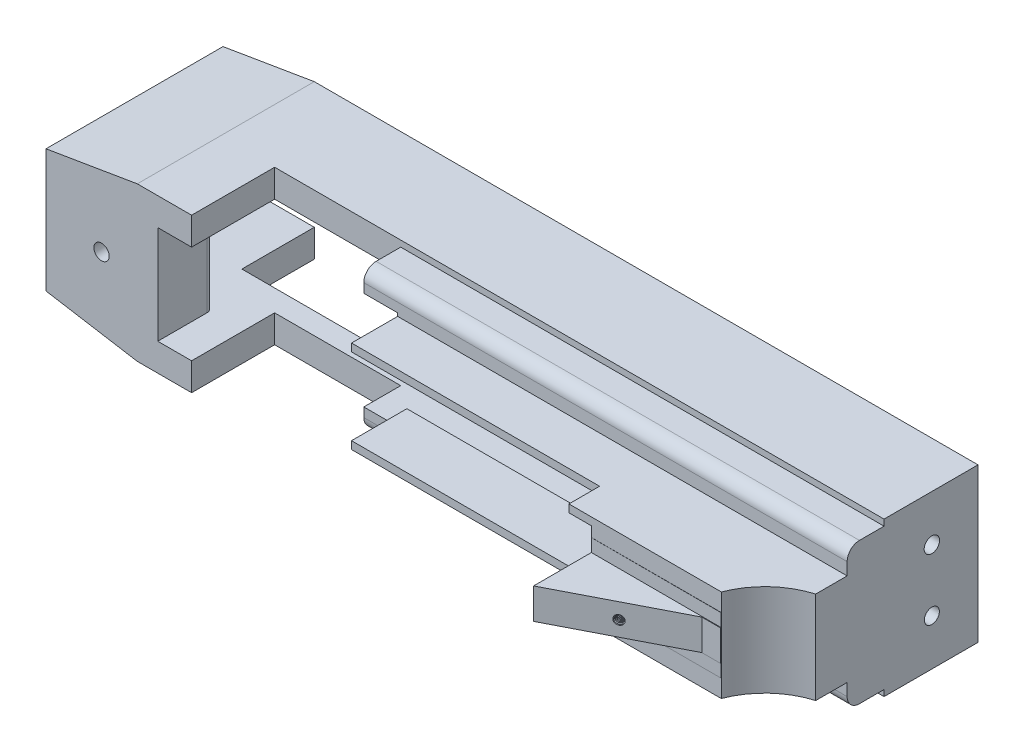
SolidWorks part; units mm, degrees
ref_plane "Front Plane" through (0, 0, 0) normal (0, 0, 1) x (1, 0, 0)
ref_plane "Top Plane" through (0, 0, 0) normal (0, 1, 0) x (1, 0, 0)
ref_plane "Right Plane" through (0, 0, 0) normal (1, 0, 0) x (0, 0, -1)
sketch "Sketch1" plane through (0, 0, 0) normal (0, 0, 1) x (1, 0, 0)
  line L0 (0, 0) -> (245.5, 0)
  line L1 (245.5, 0) -> (245.5, 50)
  line L2 (245.5, 50) -> (0, 50)
  line L3 (0, 50) -> (0, 0)
  dimension "D1" = 245.5
  dimension "D2" = 50
extrude "Boss-Extrude1" add sketch "Sketch1" along normal blind 57.55
sketch "Sketch2" plane through (0, 0, 0) normal (0, 0, -1) x (-1, 0, 0)
  line L0 (0, 9) -> (-205, 9)
  line L1 (0, 50) -> (0, 0) construction
  line L2 (-205, 9) -> (-205, 41)
  line L3 (-205, 41) -> (0, 41)
  line L4 (0, 41) -> (0, 9)
  line L5 (0, 0) -> (-245.5, 0) construction
  line L6 (-245.5, 50) -> (0, 50) construction
  dimension "D1" = 9
  dimension "D2" = 9
  dimension "D3" = 205
extrude "Cut-Extrude1" cut sketch "Sketch2" against normal blind 39.55
sketch "Sketch3" plane through (0, 0, 39.55) normal (0, 0, -1) x (-1, 0, 0)
  line L0 (-10, 9) -> (0, 9)
  line L1 (-205, 9) -> (0, 9) construction
  line L2 (0, 9) -> (0, 41)
  line L3 (0, 41) -> (-10, 41)
  line L4 (0, 41) -> (-205, 41) construction
  line L5 (-10, 41) -> (-10, 9)
  dimension "D1" = 10
extrude "Cut-Extrude2" cut sketch "Sketch3" against normal blind 5
sketch "Sketch4" plane through (0, 0, 39.55) normal (0, 0, -1) x (-1, 0, 0)
  line L0 (0, 9) -> (0, 41) construction
  line L1 (-205, 9) -> (-10, 9) construction
  circle A0 centre (-18.055, 25) radius 2.4875
  dimension "D1" = 4.975
  dimension "D2" = 18.055
  dimension "D3" = 16
extrude "Cut-Extrude3" cut sketch "Sketch4" against normal through all
sketch "Sketch5" plane through (0, 0, 0) normal (0, 0, -1) x (-1, 0, 0)
  line L1 (0, 50) -> (0, 41) construction
  line L4 (0, 45.028) -> (-29.689, 50)
  line L5 (-245.5, 50) -> (0, 50) construction
  line L7 (0, 45.028) -> (0, 51.6223)
  line L8 (0, 51.6223) -> (-29.689, 51.6223)
  line L9 (-29.689, 51.6223) -> (-29.689, 50)
extrude "Cut-Extrude4" cut sketch "Sketch5" against normal through all
sketch "Sketch6" plane through (0, 0, 0) normal (0, 0, -1) x (-1, 0, 0)
  line L1 (0, 9) -> (0, 0) construction
  line L4 (0, 4.972) -> (-29.689, 0)
  line L5 (0, 0) -> (-245.5, 0) construction
  line L7 (-29.689, 0) -> (0.6137, 0)
  line L8 (0.6137, 0) -> (0.6137, 4.972)
  line L9 (0.6137, 4.972) -> (0, 4.972)
extrude "Cut-Extrude5" cut sketch "Sketch6" against normal through all
sketch "Sketch7" plane through (0, 0, 0) normal (0, 0, -1) x (-1, 0, 0)
  line L0 (-29.689, 0) -> (-29.689, 9)
  line L1 (-29.689, 0) -> (-245.5, 0) construction
  line L2 (-205, 9) -> (0, 9) construction
  line L3 (0, 9) -> (0, 4.972) construction
  line L4 (-29.689, 9) -> (-112, 9)
  line L5 (-112, 9) -> (-112, 0)
  line L6 (-112, 0) -> (-29.689, 0)
  point P8 (-112, 4.5)
  dimension "D1" = 29.689
  dimension "D2" = 82.311
extrude "Cut-Extrude6" cut sketch "Sketch7" against normal blind 23.55
sketch "Sketch8" plane through (0, 0, 39.55) normal (0, 0, -1) x (-1, 0, 0)
  line L0 (-37.342, 9) -> (-37.342, 41)
  line L1 (-205, 9) -> (-10, 9) construction
  line L2 (-10, 41) -> (-205, 41) construction
  line L3 (0, 9) -> (0, 41) construction
  line L4 (-37.342, 9) -> (-99.342, 9)
  line L5 (-99.342, 9) -> (-99.342, 41)
  line L6 (-99.342, 41) -> (-37.342, 41)
  dimension "D1" = 37.342
  dimension "D2" = 62
extrude "Cut-Extrude7" cut sketch "Sketch8" against normal through all
sketch "Sketch9" plane through (0, 0, 39.55) normal (0, 0, -1) x (-1, 0, 0)
  line L0 (-99.342, 13.5) -> (-132.342, 13.5)
  line L1 (-99.342, 41) -> (-99.342, 9) construction
  line L2 (-132.342, 13.5) -> (-132.342, 36.5)
  line L3 (-132.342, 36.5) -> (-99.342, 36.5)
  line L4 (-99.342, 36.5) -> (-99.342, 13.5)
  line L5 (-205, 9) -> (-99.342, 9) construction
  line L6 (-99.342, 41) -> (-205, 41) construction
  dimension "D1" = 4.5
  dimension "D2" = 4.5
  dimension "D3" = 33
extrude "Cut-Extrude8" cut sketch "Sketch9" against normal through all
sketch "Sketch10" plane through (0, 0, 39.55) normal (0, 0, -1) x (-1, 0, 0)
  line L0 (-132.342, 36.25) -> (-184.342, 36.25)
  line L1 (-132.342, 36.5) -> (-132.342, 13.5) construction
  line L2 (-184.342, 36.25) -> (-184.342, 13.75)
  line L3 (-184.342, 13.75) -> (-132.342, 13.75)
  line L4 (-132.342, 13.75) -> (-132.342, 36.25)
  line L5 (-205, 9) -> (-99.342, 9) construction
  line L6 (-99.342, 41) -> (-205, 41) construction
  dimension "D1" = 4.75
  dimension "D2" = 4.75
  dimension "D3" = 52
extrude "Cut-Extrude9" cut sketch "Sketch10" against normal through all
sketch "Sketch11" plane through (0, 0, 39.55) normal (0, 0, -1) x (-1, 0, 0)
  line L0 (-184.342, 13.75) -> (-187.342, 13.75)
  line L1 (-187.342, 13.75) -> (-187.342, 34.2927)
  line L2 (-187.342, 34.2927) -> (-184.342, 36.25)
  line L3 (-184.342, 36.25) -> (-184.342, 13.75)
  dimension "D1" = 3
extrude "Cut-Extrude10" cut sketch "Sketch11" against normal blind 3
sketch "Sketch12" plane through (0, 50, 0) normal (0, 1, 0) x (1, 0, 0)
  line L0 (47.342, -57.55) -> (47.342, -30.55)
  line L1 (245.5, -57.55) -> (29.689, -57.55) construction
  line L2 (0, -57.55) -> (0, 0) construction
  line L3 (47.342, -30.55) -> (88.342, -30.55)
  line L4 (88.342, -30.55) -> (88.342, -57.55)
  line L5 (88.342, -57.55) -> (47.342, -57.55)
  point P7 (88.342, -44.05)
  dimension "D1" = 47.342
  dimension "D2" = 41
  dimension "D3" = 27
extrude "Cut-Extrude11" cut sketch "Sketch12" against normal through all
sketch "Sketch13" plane through (0, 50, 0) normal (0, 1, 0) x (1, 0, 0)
  line L0 (88.342, -57.55) -> (88.342, -42.55)
  line L1 (88.342, -57.55) -> (88.342, -30.55) construction
  line L2 (88.342, -42.55) -> (99.342, -42.55)
  line L3 (99.342, -42.55) -> (99.342, -57.55)
  line L4 (245.5, -57.55) -> (88.342, -57.55) construction
  line L5 (99.342, -57.55) -> (88.342, -57.55)
  dimension "D1" = 15
  dimension "D2" = 11
extrude "Cut-Extrude12" cut sketch "Sketch13" against normal through all
sketch "Sketch14" plane through (0, 50, 0) normal (0, 1, 0) x (1, 0, 0)
  line L0 (99.342, -57.55) -> (99.342, -42.55)
  line L1 (99.342, -42.55) -> (245.5, -42.55)
  line L2 (245.5, -57.55) -> (245.5, 0) construction
  line L3 (245.5, -42.55) -> (245.5, -57.55)
  line L4 (245.5, -57.55) -> (99.342, -57.55)
extrude "Cut-Extrude13" cut sketch "Sketch14" against normal blind 10
sketch "Sketch15" plane through (0, 40, 0) normal (0, 1, 0) x (1, 0, 0)
  line L0 (180, -57.55) -> (180, -86.52)
  line L1 (99.342, -57.55) -> (245.5, -57.55) construction
  line L2 (180, -86.52) -> (245.5, -86.52)
  line L3 (245.5, -86.52) -> (245.5, -57.55)
  line L4 (245.5, -57.55) -> (180, -57.55)
  line L5 (0, -57.55) -> (0, 0) construction
  dimension "D1" = 28.97
  dimension "D2" = 180
extrude "Boss-Extrude2" add sketch "Sketch15" against normal blind 30
sketch "Sketch17" plane through (0, 40, 0) normal (0, 1, 0) x (1, 0, 0)
  line L0 (180, -67.55) -> (187, -67.55)
  line L1 (180, -57.55) -> (180, -86.52) construction
  line L2 (99.342, -57.55) -> (180, -57.55) construction
  line L3 (187, -67.55) -> (187, -86.52)
  line L4 (180, -86.52) -> (245.5, -86.52) construction
  line L5 (187, -86.52) -> (180, -86.52)
  line L6 (180, -86.52) -> (180, -67.55)
  dimension "D1" = 10
  dimension "D2" = 7
extrude "Cut-Extrude14" cut sketch "Sketch17" against normal through all
sketch "Sketch18" plane through (0, 0, 57.55) normal (0, 0, -1) x (-1, 0, 0)
  line L0 (-180, 13.75) -> (-184.342, 13.75)
  line L1 (-184.342, 13.75) -> (-184.342, 36.25)
  line L2 (-184.342, 36.25) -> (-180, 36.25)
  line L3 (-180, 36.25) -> (-180, 13.75)
extrude "Cut-Extrude15" cut sketch "Sketch18" against normal through all
sketch "Sketch20" plane through (0, 0, 67.55) normal (0, 0, 1) x (1, 0, 0)
  line L0 (184.342, 36.25) -> (187, 36.25)
  line L1 (187, 10) -> (187, 40) construction
  line L2 (184.342, 36.25) -> (184.342, 13.75)
  line L3 (184.342, 13.75) -> (187, 13.75)
  line L4 (187, 13.75) -> (187, 36.25)
extrude "Cut-Extrude16" cut sketch "Sketch20" against normal blind 18
sketch "Sketch21" plane through (0, 40, 0) normal (0, 1, 0) x (1, 0, 0)
  line L1 (245.5, -86.52) -> (245.5, -42.55) construction
  line L2 (245.5, -67.597) -> (245.5, -86.52)
  line L3 (245.5, -86.52) -> (187, -86.52)
  line L5 (245.5, -67.597) -> (187, -67.55)
  line L7 (187, -67.55) -> (176.1532, -67.55)
  line L8 (176.1532, -67.55) -> (176.1532, -86.52)
  line L9 (176.1532, -86.52) -> (187, -86.52)
  dimension "D1" = 18.923
extrude "Cut-Extrude17" cut sketch "Sketch21" against normal blind 10
sketch "Sketch27" plane through (0, 40, 0) normal (0, 1, 0) x (1, 0, 0)
  line L1 (180, -57.55) -> (180, -67.55) construction
  line L2 (180, -67.519) -> (245.5, -67.519)
  line L3 (245.5, -67.597) -> (245.5, -42.55) construction
  line L4 (187, -67.55) -> (180, -67.55) construction
  line L5 (180, -67.519) -> (180, -67.55)
  line L6 (180, -67.55) -> (245.5, -67.597)
  line L7 (245.5, -67.597) -> (245.5, -67.519)
  dimension "D1" = 0.031
extrude "Cut-Extrude21" cut sketch "Sketch27" against normal blind 5.804
sketch "Sketch22" plane through (0, 10, 0) normal (0, -1, 0) x (1, 0, 0)
  line L0 (187, 67.55) -> (245.5, 67.55)
  line L1 (245.5, 86.52) -> (245.5, 57.55) construction
  line L2 (245.5, 67.55) -> (245.5, 86.52)
  line L3 (245.5, 86.52) -> (187, 86.52)
  line L4 (187, 86.52) -> (187, 67.55)
extrude "Cut-Extrude18" cut sketch "Sketch22" against normal blind 10
sketch "Sketch23" plane through (0, 30, 0) normal (0, 1, 0) x (1, 0, 0)
  line L9 (187, -67.55) -> (187, -86.52) construction
  line L12 (223.471, -67.772) -> (187, -86.52)
  line L13 (223.471, -67.772) -> (245.5, -67.772)
  line L14 (187, -86.52) -> (245.5, -86.52)
  line L15 (245.5, -86.52) -> (245.5, -67.772)
  dimension "D2" = 36.471
extrude "Cut-Extrude20" cut sketch "Sketch23" against normal through all
sketch "Sketch29" plane through (74.2658, 0, 144.4713) normal (0.4572, 0, 0.8894) x (0.8894, 0, -0.4572)
  line L0 (126.7571, 20) -> (126.7571, 30) construction
  line L1 (167.7646, 30) -> (126.7571, 30) construction
  circle A0 centre (147.7571, 24.882) radius 1.5
  dimension "D3" = 3
  dimension "D1" = 21
  dimension "D2" = 5.118
extrude "Cut-Extrude22" cut sketch "Sketch29" against normal blind 8.5
sketch "Sketch31" plane through (0, 0, 0) normal (0, -1, 0) x (1, 0, 0)
  line L0 (88.342, 30.55) -> (245.5, 30.55)
  line L2 (245.5, 57.55) -> (245.5, 0) construction
  line L3 (245.5, 30.55) -> (245.5, 57.55)
  line L4 (245.5, 57.55) -> (99.342, 57.55)
  line L5 (99.342, 57.55) -> (88.342, 57.55)
  line L6 (88.342, 57.55) -> (88.342, 30.55)
extrude "Cut-Extrude23" cut sketch "Sketch31" against normal blind 2
sketch "Sketch32" plane through (0, 2, 0) normal (0, -1, 0) x (1, 0, 0)
  line L0 (99.342, 42.55) -> (245.5, 42.55)
  line L1 (245.5, 30.55) -> (245.5, 57.55) construction
  line L2 (245.5, 42.55) -> (245.5, 57.55)
  line L3 (245.5, 57.55) -> (99.342, 57.55)
  line L4 (99.342, 57.55) -> (99.342, 42.55)
extrude "Cut-Extrude24" cut sketch "Sketch32" against normal blind 8
fillet "Fillet2" radius 4 1 edges at (166.921, 2, 42.55)
sketch "Sketch35" plane through (0, 0, 67.55) normal (0, 0, 1) x (1, 0, 0)
  line L0 (245.5, 20) -> (245.5, 15.797)
  line L1 (245.5, 15.797) -> (187, 15.797)
  line L2 (187, 20) -> (187, 13.75) construction
  line L3 (187, 15.797) -> (187, 20)
  line L4 (187, 20) -> (245.5, 20)
extrude "Boss-Extrude4" add sketch "Sketch35" along normal blind 0.08
sketch "Sketch37" plane through (0, 50, 0) normal (0, 1, 0) x (1, 0, 0)
  line L0 (88.342, -30.55) -> (245.5, -30.55)
  line L1 (245.5, -42.55) -> (245.5, 0) construction
  line L2 (245.5, -30.55) -> (245.5, -42.55)
  line L3 (245.5, -42.55) -> (88.342, -42.55) construction
  line L4 (245.5, -42.55) -> (88.342, -42.55)
  line L5 (88.342, -42.55) -> (88.342, -30.55)
extrude "Cut-Extrude25" cut sketch "Sketch37" against normal blind 2
fillet "Fillet3" radius 4 1 edges at (166.921, 48, 42.55)
sketch "Sketch38" plane through (205, 0, 0) normal (-1, 0, 0) x (0, 0, 1)
  line L0 (30.55, 0) -> (0, 0) construction
  line L1 (30.55, 50) -> (0, 50) construction
  line L2 (0, 41) -> (0, 9) construction
  circle A0 centre (15, 15) radius 2.4445
  circle A1 centre (15, 35) radius 2.5019
  dimension "D1" = 15
  dimension "D2" = 15
  dimension "D3" = 15
  dimension "D4" = 15
extrude "Cut-Extrude26" cut sketch "Sketch38" against normal through all
sketch "Sketch39" plane through (0, 0, 67.772) normal (0, 0, 1) x (1, 0, 0)
  line L0 (229.571, 20) -> (229.571, 30)
  line L1 (223.471, 20) -> (245.5, 20) construction
  line L2 (245.5, 30) -> (223.471, 30) construction
  line L3 (223.471, 20) -> (223.471, 30) construction
  line L4 (229.571, 20) -> (229.571, 12.2217)
  line L6 (253.2973, 12.2217) -> (254.0062, 41.842)
  line L7 (254.0062, 41.842) -> (229.571, 41.842)
  line L8 (229.571, 41.842) -> (229.571, 30)
  line L9 (229.571, 12.2217) -> (229.571, 4.0695)
  line L10 (229.571, 4.0695) -> (253.2973, 4.0695)
  line L11 (253.2973, 4.0695) -> (253.2973, 12.2217)
  dimension "D1" = 6.1
extrude "Cut-Extrude27" cut sketch "Sketch39" against normal blind 15
sketch "Sketch42" plane through (0, 10, 0) normal (0, -1, 0) x (1, 0, 0)
  line L0 (229.571, 67.55) -> (229.571, 52.772)
  line L1 (229.571, 52.772) -> (245.5, 52.772)
  arc A0 (245.5, 52.772) -> (229.571, 67.55) centre (252.4707, 76.2594) cw
  dimension "D1" = 24.5
extrude "Boss-Extrude5" add sketch "Sketch42" against normal blind 30
thread "Thread1" pitch 0.5 method extrude profile "Thread Profile2" start angle 0, offset 0, length 6.5, pitch 0.5, diameter 3
ref_plane "Plane2" through (204.3428, 24.882, 77.6049) normal (0, -1, 0) x (-0.8894, 0, 0.4572)
sketch "Thread Profile2" plane through (204.3428, 24.882, 77.6049) normal (0, -1, 0) x (-0.8894, 0, 0.4572)
  line L0 (0, 0) -> (0, 0.5) construction
  line L11 (0, 0) -> (0, 0.4375)
  line L12 (0, 0.4375) -> (-0.2706, 0.2812)
  line L13 (-0.2706, 0.2812) -> (-0.2706, 0.1562)
  line L15 (-0.2706, 0.1562) -> (0, 0)
  line L17 (-0.2706, 0.2187) -> (0, 0.2187) construction
  point P2 (0, 0)
  dimension "Pitch" = 0.5
  dimension "Profile_Angle" = 60
  dimension "Profile_Land" = 0.125
  dimension "Profile_Height" = 0.2706
fillet "Fillet4" radius 4 1 edges at (10, 25, 39.55)
sketch "Sketch43" plane through (0, 0, 57.55) normal (0, 0, 1) x (1, 0, 0)
  line L0 (37.342, 9) -> (36.342, 9)
  line L1 (37.342, 9) -> (37.342, 41)
  line L2 (37.342, 41) -> (36.342, 41)
  line L3 (36.342, 41) -> (36.342, 9)
  dimension "D1" = 1
extrude "Cut-Extrude28" cut sketch "Sketch43" against normal through all
fillet "Fillet7" radius 2 1 edges at (36.342, 25, 39.55)
sketch "Sketch44" plane through (0, 0, 44.55) normal (0, 0, -1) x (-1, 0, 0)
  line L0 (0, 41) -> (-10, 41)
  line L1 (-10, 41) -> (-10, 9)
  line L2 (-10, 41) -> (-10, 9) construction
  line L3 (-10, 9) -> (0, 9)
  line L4 (0, 9) -> (0, 41)
extrude "Cut-Extrude29" cut sketch "Sketch44" against normal blind 2.85
sketch "Sketch46" plane through (0, 0, 39.55) normal (0, 0, -1) x (-1, 0, 0)
  line L0 (-187.342, 37.5) -> (-91.8743, 37.5)
  line L1 (-187.342, 37.5) -> (-187.342, 12.5)
  line L2 (-187.342, 12.5) -> (-91.8743, 12.5)
  line L3 (-91.8743, 12.5) -> (-91.8743, 37.5)
  line L4 (-99.342, 41) -> (-205, 41) construction
  line L5 (-205, 9) -> (-99.342, 9) construction
  dimension "D1" = 3.5
  dimension "D2" = 3.5
extrude "Cut-Extrude30" cut sketch "Sketch46" against normal through all
